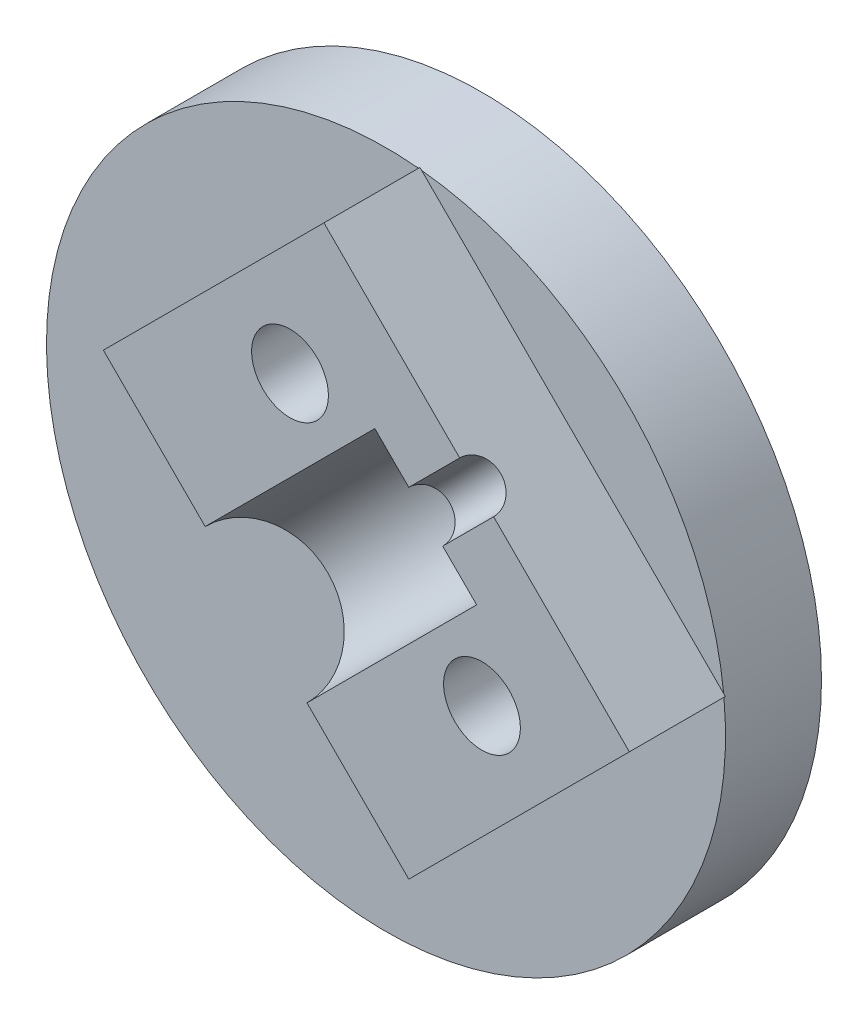
SolidWorks part; units mm, degrees
ref_plane "前视基准面" through (0, 0, 0) normal (0, 0, 1) x (1, 0, 0)
ref_plane "上视基准面" through (0, 0, 0) normal (0, 1, 0) x (1, 0, 0)
ref_plane "右视基准面" through (0, 0, 0) normal (1, 0, 0) x (0, 0, -1)
sketch "草图1" plane through (0, 0, 0) normal (0, 0, 1) x (1, 0, 0)
  circle A0 centre (0, 0) radius 14.1493
  circle A1 centre (0, -8) radius 1.6
  circle A2 centre (8, 0) radius 1.6
  circle A3 centre (0, 8) radius 1.6
  circle A4 centre (-8, 0) radius 1.6
  dimension "D1" = 3.2
  dimension "D2" = 3.2
  dimension "D3" = 3.2
  dimension "D4" = 3.2
extrude "凸台-拉伸1" add sketch "草图1" along normal blind 4
ref_axis "基准轴1" through (0, 0, 26.8028) along (0, 0, -1)
ref_plane "基准面4" through (0, 0, 0) normal (0.7071, 0.7071, 0) x (0, 0, -1)
sketch "草图3" plane through (0, 0, 0) normal (0.7071, 0.7071, 0) x (0, 0, -1)
  line L5 (-8, 3) -> (-8, -9)
  line L6 (-8, -9) -> (-4, -9)
  line L7 (-4, 14.1493) -> (-4, -14.1493) construction
  line L8 (-4, -9) -> (-4, 9)
  line L9 (-4, 9) -> (-8, 9)
  line L10 (-8, 9) -> (-8, 3)
  circle A0 centre (-8, 0) radius 3
  dimension "D3" = 0
  dimension "D4" = 6
  dimension "D1" = 9
  dimension "D2" = 9
extrude "凸台-拉伸2" add sketch "草图3" along normal blind 11 and the other way blind 2 contours A0 L6 region at (-4.2426, 4.2426, 7.8156)
sketch "草图4" plane through (0, 0, 8) normal (0, 0, 1) x (1, 0, 0)
  circle A0 centre (8, 0) radius 1.6
  circle A1 centre (0, 8) radius 1.6
  dimension "D1" = 3.2
  dimension "D2" = 3.2
extrude "切除-拉伸1" cut sketch "草图4" against normal blind 10
sketch "草图5" plane through (7.7782, 7.7782, 0) normal (0.7071, 0.7071, 0) x (0, 0, -1)
  line L0 (-8, 9) -> (-8, 3) construction
  line L1 (-8, -3) -> (-8, 3)
  circle A0 centre (-8, 0) radius 1
  circle A1 centre (-8, 0) radius 3
  arc M1 (-8, 3) -> (-8, -3) centre (-8, 0) cw
  dimension "D1" = 2
  dimension "D2" = 0
  dimension "D3" = 3
extrude "凸台-拉伸3" add sketch "草图5" against normal blind 3 contours A0 L1 M1 region at (7.7782, 7.7782, 6.6207)
